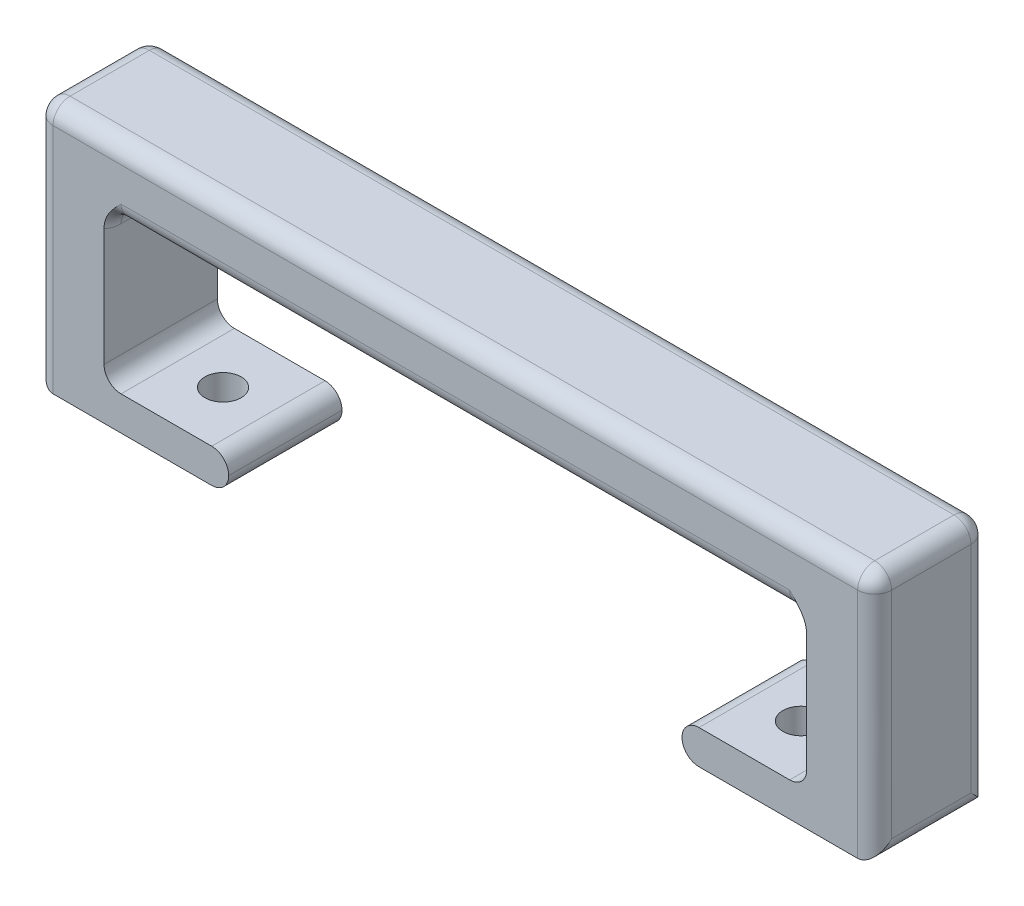
SolidWorks part; units mm, degrees
ref_plane "Plano frontal" through (0, 0, 0) normal (0, 0, 1) x (1, 0, 0)
ref_plane "Plano superior" through (0, 0, 0) normal (0, 1, 0) x (1, 0, 0)
ref_plane "Plano direito" through (0, 0, 0) normal (1, 0, 0) x (0, 0, -1)
sketch "Esboço1" plane through (0, 0, 0) normal (0, 0, 1) x (1, 0, 0)
  line L0 (0, 0) -> (0, 24544.4371) construction
  line L1 (-37, -3) -> (-20, -3)
  line L2 (-20, -3) -> (-20, 0)
  line L3 (-20, 0) -> (-31, 0)
  line L4 (-31, 0) -> (-31, 13)
  line L5 (-31, 13) -> (31, 13)
  line L6 (-37, -3) -> (-37, 19)
  line L7 (-37, 19) -> (37, 19)
  line L8 (37, -3) -> (37, 19)
  line L9 (31, 0) -> (31, 13)
  line L10 (20, 0) -> (31, 0)
  line L11 (20, -3) -> (20, 0)
  line L12 (37, -3) -> (20, -3)
  point P12 (0, 19)
  point P14 (0, 13)
  dimension "D1" = 16
  dimension "D2" = 6
  dimension "D3" = 3
  dimension "D4" = 6
  dimension "D5" = 74
  dimension "D6" = 20
extrude "Ressalto-extrusão1" add sketch "Esboço1" along normal blind 10
sketch "Esboço2" plane through (0, 0, 0) normal (0, 1, 0) x (1, 0, 0)
  line L0 (0, 0) -> (0, 50000) construction
  line L1 (-31, 0) -> (-20, 0) construction
  line L2 (-31, 0) -> (-31, -10) construction
  line L3 (-31, -10) -> (-20, -10) construction
  line L4 (-20, 0) -> (-20, -10) construction
  line L5 (-25.5, -10) -> (-25.5, 0) construction
  line L6 (-31, -5) -> (-20, -5) construction
  circle A0 centre (-25.5, -5) radius 1.6
  circle A1 centre (25.5, -5) radius 1.6
  point P142 (-25.5, -5)
  dimension "D1" = 3.2
extrude "Corte-extrusão1" cut sketch "Esboço2" against normal up to next
fillet "Filete1" radius 1.5 4 edges at (0, 13, 10) (0, 13, 0) (0, 19, 0) (0, 19, 10)
fillet "Filete2" radius 1.5 18 edges at (37, 7.25, 10) (37, 18.5607, 9.5607) (37, 7.25, 0) (37, 18.5607, 0.4393) (-37, 7.25, 10) (-37, 18.5607, 9.5607) (-37, 7.25, 0) (-37, 18.5607, 0.4393) (37, 19, 5) (-37, 19, 5) (-20, -3, 5) (20, -3, 5) (-20, 0, 5) (20, 0, 5) (31, 0, 5) (-31, 0, 5) (-37, -3, 5) (37, -3, 5)
fillet "Filete3" radius 1.5 6 edges at (-31, 13.4393, 9.5607) (-31, 13.4393, 0.4393) (31, 13.4393, 9.5607) (31, 13.4393, 0.4393) (-31, 13, 5) (31, 13, 5)
